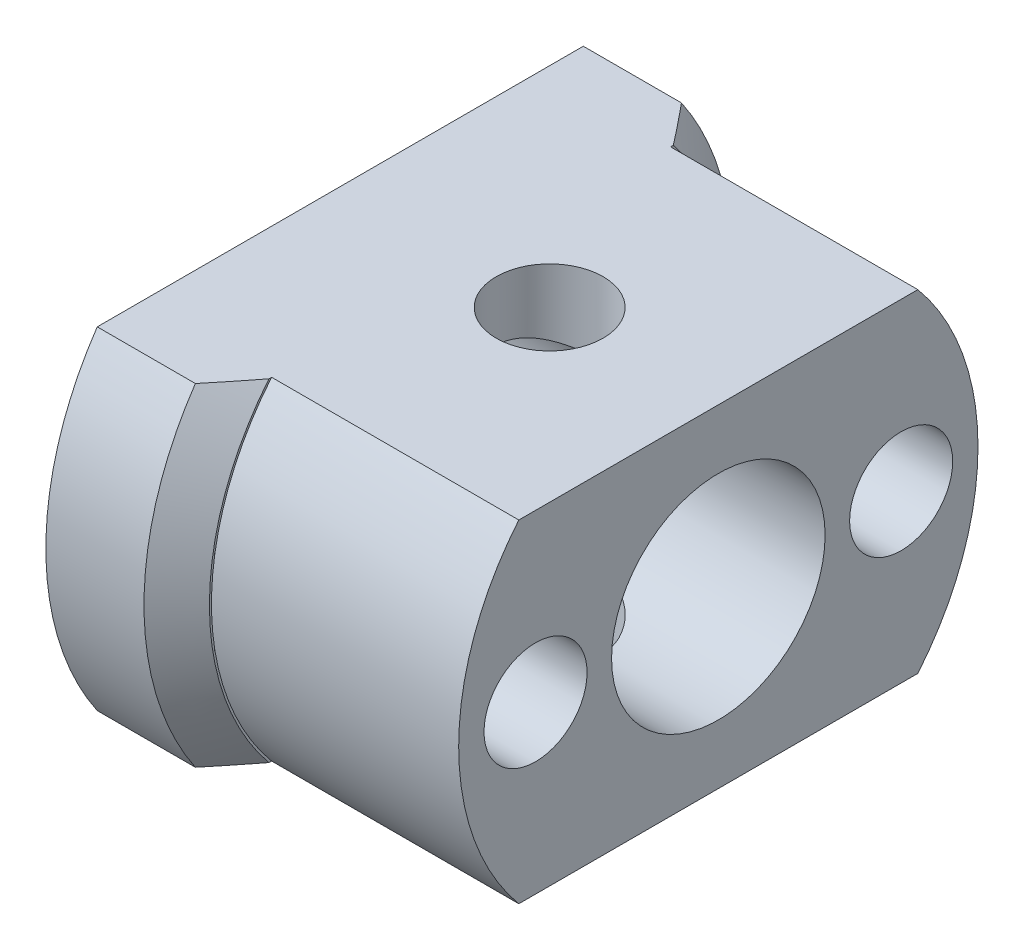
SolidWorks part; units mm, degrees
ref_plane "Front Plane" through (0, 0, 0) normal (0, 0, 1) x (1, 0, 0)
ref_plane "Top Plane" through (0, 0, 0) normal (0, 1, 0) x (1, 0, 0)
ref_plane "Right Plane" through (0, 0, 0) normal (1, 0, 0) x (0, 0, -1)
sketch "Sketch1" plane through (0, 0, 0) normal (1, 0, 0) x (0, 0, -1)
  line L0 (0, 0) -> (0, 0.7417) construction
  line L1 (-3.2639, 0) -> (-6.35, 0) construction
  circle A0 centre (0, 0) radius 6.35
  circle A1 centre (0, 0) radius 6.35
  circle A2 centre (0, 0) radius 3.2639
  circle A3 centre (-5.588, 0) radius 1.575
  circle A5 centre (0, 0) radius 7.9375
  circle A6 centre (5.588, 0) radius 1.575
  dimension "D1" = 12.7
  dimension "D2" = 6.5278
  dimension "D3" = 3.15
  dimension "D4" = 15.875
  dimension "D5" = 11.176
extrude "Inner Side Extrude" add sketch "Sketch1" along normal blind 2.032 contours A0 A2 A3 A6 | A5 A1 A6 A3 region at (0, 0, -3.8358) region at (0, 0, 7.713)
extrude "Outer Side Extrude" add sketch "Sketch1<3>" against normal blind 9.525 contours A0 A2 A3 A6 | A5 A0 region at (0, 0, -3.8358) region at (0, 0, 7.713)
sketch "Sketch1<3>" plane through (0, 0, 0) normal (1, 0, 0) x (0, 0, -1) same geometry as "Sketch1"
sketch "Sketch2" plane through (0, 0, 0) normal (0, 1, 0) x (1, 0, 0)
  line L0 (-9.525, 7.9375) -> (-9.525, -7.9375) construction
  line L1 (-9.525, 0) -> (0, 0) construction
  line L2 (2.032, -7.9375) -> (2.032, 7.9375) construction
  circle A0 centre (-3.1242, 0) radius 1.632
  point P0 (-9.525, 0)
  dimension "D1" = 3.2639
  dimension "D2" = 5.1562
extrude "Clevis Pin Cut" cut sketch "Sketch2" against normal through all and the other way through all
chamfer "Chamfer so Steve Doesn't cut himself" [suppressed] distance 0.3969 angle 45
sketch "Sketch3" plane through (-9.525, 0, 0) normal (1, 0, 0) x (0, 0, -1)
  circle A0 centre (0, 0) radius 9
  circle A6 centre (0, 0) radius 7.9375
  circle A7 centre (0, 0) radius 7.9375 construction
  dimension "D1" = 18
extrude "Boss-Extrude1" add sketch "Sketch3" along normal blind 4
sketch "Sketch4" plane through (-9.525, 0, 0) normal (1, 0, 0) x (0, 0, -1)
  line L0 (0, 0) -> (0, 1.7726)
  line L1 (-5.588, 2.5981) -> (-7.838, 1.299)
  line L2 (-7.838, 1.299) -> (-7.838, -1.299)
  line L3 (-7.838, -1.299) -> (-5.588, -2.5981)
  line L4 (-5.588, -2.5981) -> (-3.338, -1.299)
  line L5 (-3.338, -1.299) -> (-3.338, 1.299)
  line L6 (-3.338, 1.299) -> (-5.588, 2.5981)
  line L7 (3.338, 1.299) -> (5.588, 2.5981)
  line L8 (3.338, -1.299) -> (3.338, 1.299)
  line L9 (5.588, -2.5981) -> (3.338, -1.299)
  line L10 (7.838, -1.299) -> (5.588, -2.5981)
  line L11 (7.838, 1.299) -> (7.838, -1.299)
  line L12 (5.588, 2.5981) -> (7.838, 1.299)
  circle A0 centre (-5.588, 0) radius 2.25 construction
  circle A1 centre (5.588, 0) radius 2.25 construction
  circle M22 centre (5.588, 0) radius 1.575
  circle M24 centre (-5.588, 0) radius 1.575
  dimension "D1" = 4.5
extrude "Cut-Extrude1" cut sketch "Sketch4" along normal blind 4 contours L6 L5 L4 L3 L2 L1 M24 | L7 L12 L11 L10 L9 L8 M22 region at (-9.525, 1.889, 4.4974) region at (-9.525, 1.889, -4.4974)
chamfer "Chamfer1" distance 1 angle 45 1 edges at (-5.525, 0, -9)
sketch "Sketch5" plane through (0, 0, 0) normal (0, 0, 1) x (1, 0, 0)
  line L0 (-3.1242, -5.08) -> (-3.1242, 5.08)
  line L1 (-1.4923, 0) -> (-4.7562, 0) construction
  line L2 (6.3564, 0) -> (-6.3564, 0) construction
  line L3 (-11.3792, 9.3929) -> (5.1308, 9.3929)
  line L4 (-11.3792, 9.3929) -> (-11.3792, 5.08)
  line L5 (-11.3792, 5.08) -> (5.1308, 5.08)
  line L6 (5.1308, 9.3929) -> (5.1308, 5.08)
  line L7 (5.1308, -9.3929) -> (5.1308, -5.08)
  line L8 (-11.3792, -5.08) -> (5.1308, -5.08)
  line L9 (-11.3792, -9.3929) -> (-11.3792, -5.08)
  line L10 (-11.3792, -9.3929) -> (5.1308, -9.3929)
  point P8 (0, 0)
  point P17 (-3.1242, 0)
  dimension "D1" = 16.51
  dimension "D2" = 5.08
extrude "Cut-Extrude2" cut sketch "Sketch5" against normal through all both and the other way through all contours L6 L3 L4 L5 | L9 L10 L7 L8 region at (-3.1242, 7.2364, 0) region at (-3.1242, -7.2364, 0)
